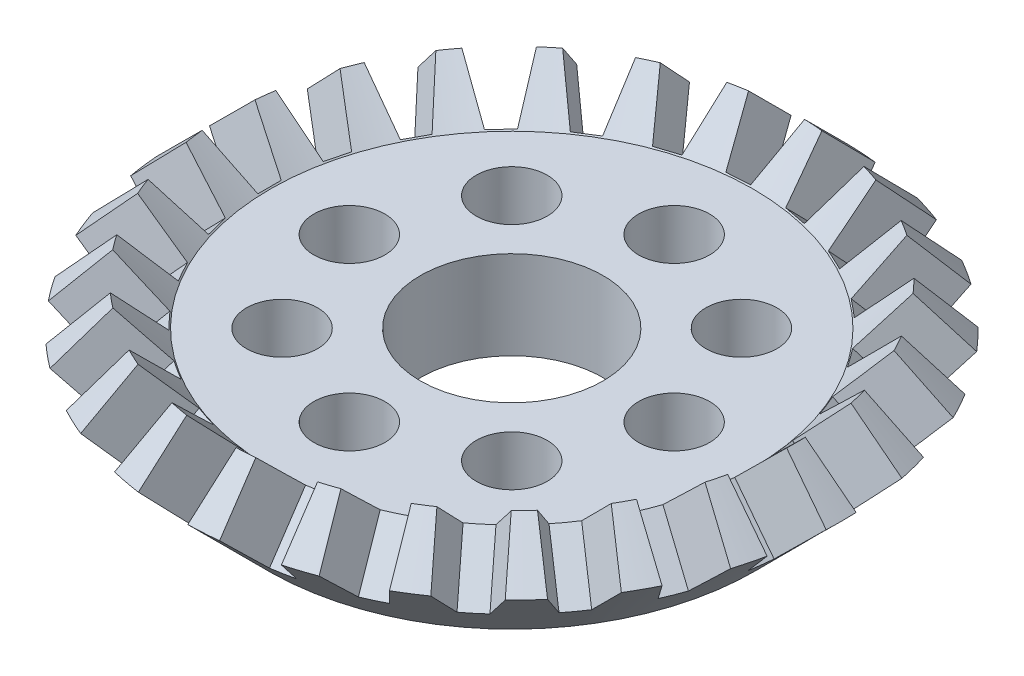
SolidWorks part; units mm, degrees
ref_plane "Front Plane" through (0, 0, 0) normal (0, 0, 1) x (1, 0, 0)
ref_plane "Top Plane" through (0, 0, 0) normal (0, 1, 0) x (1, 0, 0)
ref_plane "Right Plane" through (0, 0, 0) normal (1, 0, 0) x (0, 0, -1)
sketch "Sketch2" plane through (0, 0, 0) normal (0, 0, 1) x (1, 0, 0)
  line L6 (0, 0) -> (0, 4.3558)
  line L7 (0, 0) -> (-12, 0)
  line L9 (-12, 0) -> (-16.2426, 4.2426)
  line L14 (-16.2426, 4.2426) -> (-14.0081, 6.4771)
  line L15 (-11.8868, 4.3558) -> (-14.0081, 6.4771)
  line L16 (-11.8868, 4.3558) -> (0, 4.3558)
  dimension "D2" = 12
  dimension "D4" = 45
  dimension "D5" = 6
  dimension "D6" = 3
revolve "Revolve4" add sketch "Sketch2" angle 360 about L6
sketch "Sketch3" plane through (0, 0, 0) normal (0, 0, 1) x (1, 0, 0)
  line L0 (0, 0) -> (0, 20.4853) construction
  line L1 (0, 20.4853) -> (0, -16.6359) construction
  line L2 (0, 20.4853) -> (-22.6315, -2.1462) construction
  line L3 (-14.0081, 6.4771) -> (-16.2426, 4.2426) construction
ref_plane "Plane1" through (-6, -6, 0) normal (-0.7071, -0.7071, 0) x (0, 0, 1)
sketch "Sketch4" plane through (-6, -6, 0) normal (-0.7071, -0.7071, 0) x (0, 0, 1)
  line L0 (0, 9.4379) -> (0, 20.3385) construction
  line L1 (0, 0) -> (0, 14.4853) construction
  line L8 (-0.5759, 11.5564) -> (0.5759, 11.5564)
  line L9 (0.5759, 11.5564) -> (1.4119, 14.8882)
  line L10 (1.4119, 14.8882) -> (-1.4119, 14.8882)
  line L11 (-0.5759, 11.5564) -> (-1.4119, 14.8882)
  point P10 (0, 11.5564)
  point P11 (0, 14.0042)
  point P12 (0, 14.8882)
  point P13 (0, 17.9558)
  point P14 (0, 14.0042)
  point P15 (0, 17.9558)
extrude "Cut-Extrude11" cut sketch "Sketch4" against normal blind 10 contours L10 L11 L8 L9
sketch "Sketch5" plane through (0, 4.3558, 0) normal (0, 1, 0) x (1, 0, 0)
  line L0 (0, 0) -> (0, -8)
  circle A0 centre (0, 0) radius 4.5
  circle A1 centre (0, -8) radius 1.75
  dimension "D1" = 9
  dimension "D3" = 3.5
  dimension "D2" = 8
extrude "Cut-Extrude12" cut sketch "Sketch5" against normal blind 10 contours A0 region at (-3.092, 4.3558, -3.092)
extrude "Cut-Extrude13" cut sketch "Sketch5<3>" against normal blind 10 contours A1
sketch "Sketch5<3>" plane through (0, 4.3558, 0) normal (0, 1, 0) x (1, 0, 0) same geometry as "Sketch5"
pattern_circular "CirPattern13" count 8 over 360 about axis through (0, 20.4853, 0) along (0, -1, 0) of "Cut-Extrude13"
pattern_circular "CirPattern14" count 25 over 360 about axis through (0, 0, 0) along (0, 1, 0) of "Cut-Extrude11" reverse direction yes
